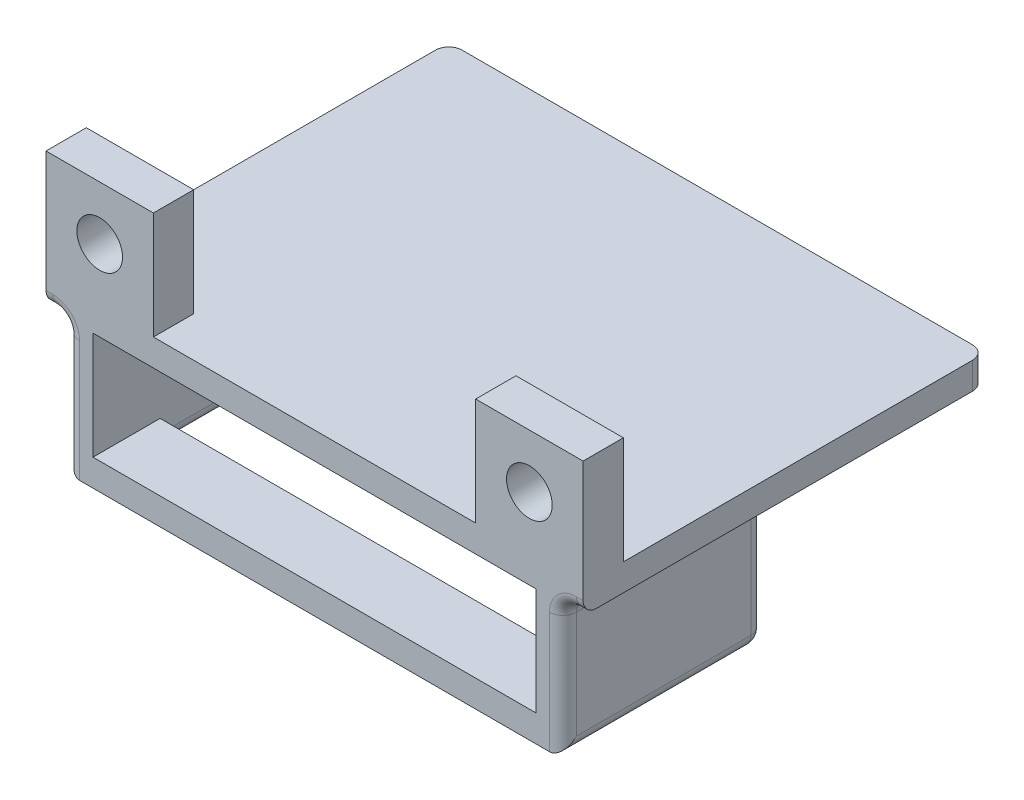
SolidWorks part; units mm, degrees
ref_plane "Front Plane" through (0, 0, 0) normal (0, 0, 1) x (1, 0, 0)
ref_plane "Top Plane" through (0, 0, 0) normal (0, 1, 0) x (1, 0, 0)
ref_plane "Right Plane" through (0, 0, 0) normal (1, 0, 0) x (0, 0, -1)
sketch "Sketch1" plane through (0, 0, 0) normal (0, 1, 0) x (1, 0, 0)
  line L1 (0, 0) -> (40, 0)
  line L2 (0, 0) -> (0, 30)
  line L3 (0, 30) -> (40, 30)
  line L4 (40, 0) -> (40, 30)
  dimension "D1" = 40
  dimension "D2" = 30
extrude "Boss-Extrude1" add sketch "Sketch1" along normal mid plane 2 contours L3 L4 L1 L2
sketch "Sketch2" plane through (0, 1, 0) normal (0, 1, 0) x (1, 0, 0)
  line L0 (0, 0) -> (40, 0) construction
  line L1 (0, 0) -> (8, 0)
  line L2 (0, 0) -> (0, 3)
  line L3 (0, 3) -> (8, 3)
  line L4 (8, 0) -> (8, 3)
  line L5 (40, 0) -> (32, 0)
  line L6 (40, 0) -> (40, 3)
  line L7 (40, 3) -> (32, 3)
  line L8 (32, 0) -> (32, 3)
  line L11 (40, 0) -> (40, 30) construction
  line L12 (0, 0) -> (0, 30) construction
  dimension "D1" = 3
  dimension "D2" = 3
  dimension "D3" = 8
  dimension "D4" = 8
extrude "Boss-Extrude2" add sketch "Sketch2" along normal blind 8
sketch "Sketch5" plane through (0, 0, -3) normal (0, 0, -1) x (-1, 0, 0)
  line L0 (0, 9) -> (0, 1) construction
  line L1 (-8, 1) -> (0, 1) construction
  point P0 (-4, 5)
  point P2 (-36, 5)
  dimension "D1" = 4
  dimension "D2" = 36
  dimension "D3" = 4
hole_wizard "M3 Clearance Hole1" positions "Sketch5" profile "Sketch4" hole size "M3" standard "ANSI Metric" end condition through all
sketch "Sketch4" plane through (4, 5, -3) normal (1, 0, 0) x (0, 1, 0)
  line L0 (0, 0) -> (0, 3)
  line L1 (0, 3) -> (1.7, 3)
  line L2 (1.7, 3) -> (1.7, 0)
  line L5 (1.7, 0) -> (0, 0)
  line L11 (0, -6.35) -> (0, 107.95) construction
  dimension "Thru Hole Dia." = 3.4
  dimension "Thru Hole Depth" = 3
sketch "Sketch7" plane through (0, 0, 0) normal (0, 0, 1) x (1, 0, 0)
  line L0 (1.5, -1) -> (1.5, -11)
  line L1 (1.5, -11) -> (38.5, -11)
  line L2 (38.5, -11) -> (38.5, -1)
  line L3 (38.5, -1) -> (36.5, -1)
  line L4 (3.5, -1) -> (3.5, -9)
  line L5 (3.5, -9) -> (36.5, -9)
  line L6 (36.5, -9) -> (36.5, -1)
  line L7 (3.5, -1) -> (1.5, -1)
  line L8 (0, 9) -> (0, -1) construction
  line L9 (40, 9) -> (40, -1) construction
  dimension "D1" = 2
  dimension "D2" = 2
  dimension "D3" = 2
  dimension "D4" = 8
  dimension "D5" = 1.5
  dimension "D6" = 1.5
extrude "Boss-Extrude3" add sketch "Sketch7" against normal blind 5 contours L5 L6 L3 L2 L1 L0 L7 L4
sketch "Sketch8" plane through (0, 0, -5) normal (0, 0, -1) x (-1, 0, 0)
  line L0 (-1.5, -11) -> (-38.5, -11) construction
  line L1 (-38.5, -1) -> (-36.5, -1)
  line L2 (-38.5, -1) -> (-38.5, -11)
  line L3 (-38.5, -11) -> (-36.5, -11)
  line L4 (-36.5, -1) -> (-36.5, -11)
  line L6 (-3.5, -1) -> (-1.5, -1)
  line L7 (-3.5, -1) -> (-3.5, -11)
  line L8 (-3.5, -11) -> (-1.5, -11)
  line L9 (-1.5, -1) -> (-1.5, -11)
  dimension "D1" = 2
extrude "Boss-Extrude4" add sketch "Sketch8" along normal blind 10
fillet "Fillet1" radius 1 19 edges at (37.5, -1, -15) (39.25, -1, 0) (2.5, -1, -15) (0.75, -1, 0) (38.5, -1, -7.5) (38.5, -6, -15) (38.5, -11, -7.5) (38.5, -6, 0) (1.5, -11, -7.5) (1.5, -6, -15) (1.5, -1, -7.5) (1.5, -6, 0) (40, 0, -30) (0, 0, -30) (37.5, -11, -15) (2.5, -11, -15) (36.5, -11, -10) (3.5, -11, -10) (20, -11, -5)
